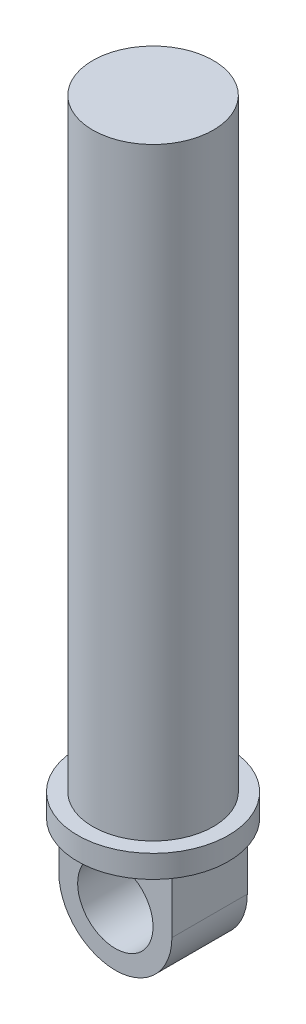
SolidWorks part; units mm, degrees
ref_plane "Front Plane" through (0, 0, 0) normal (0, 0, 1) x (1, 0, 0)
ref_plane "Top Plane" through (0, 0, 0) normal (0, 1, 0) x (1, 0, 0)
ref_plane "Right Plane" through (0, 0, 0) normal (1, 0, 0) x (0, 0, -1)
sketch "Sketch1" plane through (0, 0, 0) normal (0, 1, 0) x (1, 0, 0)
  circle A0 centre (0, 0) radius 8
  dimension "D1" = 16
extrude "Boss-Extrude1" add sketch "Sketch1" along normal blind 80
sketch "Sketch2" plane through (0, 0, 0) normal (0, -1, 0) x (1, 0, 0)
  circle A0 centre (0, 0) radius 10
  dimension "D1" = 20
extrude "Boss-Extrude2" add sketch "Sketch2" along normal blind 3
sketch "Sketch3" plane through (0, -3, 0) normal (0, -1, 0) x (1, 0, 0)
  line L1 (-7.5, -5) -> (7.5, -5)
  line L2 (-7.5, -5) -> (-7.5, 5)
  line L3 (-7.5, 5) -> (7.5, 5)
  line L4 (7.5, -5) -> (7.5, 5)
  line L5 (-7.5, -5) -> (7.5, 5) construction
  line L6 (-7.5, 5) -> (7.5, -5) construction
  point P0 (0, 0)
  dimension "D1" = 10
  dimension "D2" = 15
extrude "Boss-Extrude3" add sketch "Sketch3" along normal blind 15
sketch "Sketch4" plane through (0, 0, -5) normal (0, 0, -1) x (-1, 0, 0)
  line L0 (-7.5, -18) -> (-7.5, -3) construction
  line L1 (7.5, -18) -> (-7.5, -18) construction
  circle A0 centre (0, -10.5) radius 5
  dimension "D1" = 10
  dimension "D2" = 7.5
  dimension "D3" = 7.5
extrude "Cut-Extrude1" cut sketch "Sketch4" against normal blind 15
fillet "Fillet1" radius 7.5 2 edges at (-7.5, -18, 0) (7.5, -18, 0)
